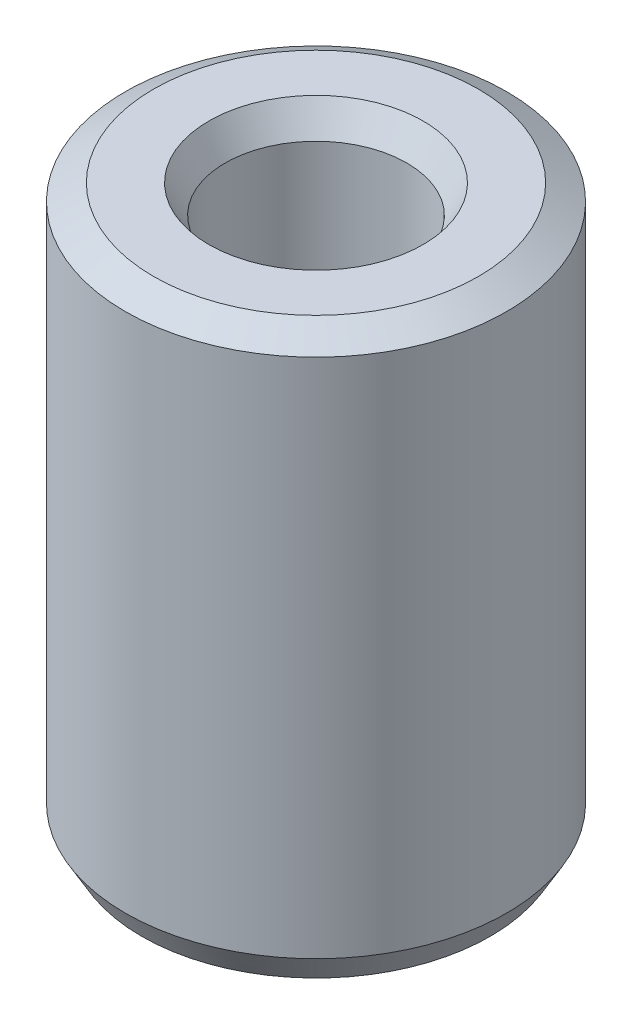
SolidWorks part; units mm, degrees
ref_plane "Front Plane" through (0, 0, 0) normal (0, 0, 1) x (1, 0, 0)
ref_plane "Top Plane" through (0, 0, 0) normal (0, 1, 0) x (1, 0, 0)
ref_plane "Right Plane" through (0, 0, 0) normal (1, 0, 0) x (0, 0, -1)
sketch "Sketch1" plane through (0, 0, 0) normal (0, 1, 0) x (1, 0, 0)
  circle A0 centre (0, 0) radius 5
  dimension "SLEEVE_OD" = 10
extrude "Boss-Extrude1" add sketch "Sketch1" along normal blind 14.8337
sketch "Sketch2" plane through (0, 0, 0) normal (0, 1, 0) x (1, 0, 0)
  circle A0 centre (0, 0) radius 2.3824
  dimension "BORE_D" = 4.7648
extrude "Cut-Extrude1" cut sketch "Sketch2" along normal through all
chamfer "Chamfer1" distance 0.4275 angle 60 4 edges at (0, 14.8337, 2.3824) (0, 0, 2.3824) (0, 0, 5) (0, 14.8337, 5) first distance on face at (0, 14.8337, 2.3824) first distance on face at (0, 0, 2.3824) first distance on face at (0, 14.8337, 5)
